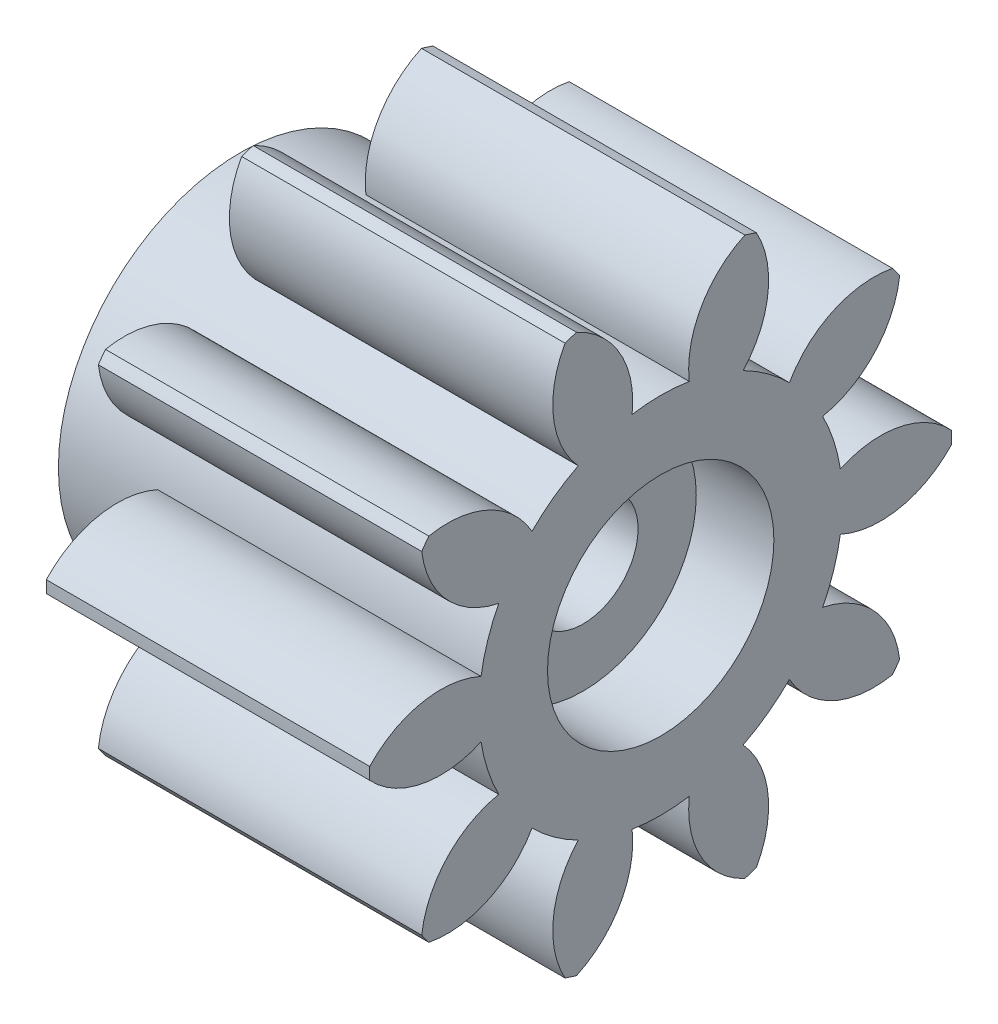
SolidWorks part; units mm, degrees
material "7075-O (SS)"
ref_plane "Plane1" through (0, 0, 0) normal (0, 0, 1) x (1, 0, 0)
ref_plane "Plane2" through (0, 0, 0) normal (0, 1, 0) x (1, 0, 0)
ref_plane "Plane3" through (0, 0, 0) normal (1, 0, 0) x (0, 0, -1)
sketch "HoldingSke" plane through (0, 0, 0) normal (0, 1, 0) x (1, 0, 0)
  line L0 (0, 0) -> (0.6565, -0.1158)
  line L1 (-15, 0) -> (100, 0) construction
  line L2 (0, 0) -> (-2.1039, 2.3779)
  line L3 (0, 0) -> (-11.863, 4.5341)
  line L4 (0, 0) -> (8.5048, 1.4996)
  line L5 (0, 0) -> (-46.8476, -17.4728)
  line L6 (0, 0) -> (-8.2896, -5.593)
  line L7 (-2.1039, 2.3779) -> (8.6589, 51.2074)
  line L8 (-76.2, 54.61) -> (-76.1, 54.61)
  line L9 (-71.009, 38.7566) -> (-53.1078, 45.2721)
  line L10 (-76.2, 71.12) -> (104.1128, 71.12)
  line L11 (0, 0) -> (-10, 0)
  line L12 (-76.2, 101.6) -> (-76.147, 101.6)
  line L13 (24.9733, 27.94) -> (52.9518, 28.4284)
  line L14 (24.9733, 27.94) -> (24.9743, 27.94)
  line L15 (24.9733, 27.94) -> (100.4006, 29.5858)
  line L16 (-63.627, -1.5) -> (-12.827, -1.5)
  circle A0 centre (0, 0) radius 0.4
  circle A1 centre (0, 0) radius 5.624
  circle A2 centre (0, 0) radius 37.5
  circle A3 centre (0, 0) radius 0.4
  dimension "MHD" = 11.248
  dimension "Hub_dia" = 75
  dimension "Bore" = 0.8
  dimension "MBD" = 0.8
  dimension "Num_teeth" = 10
  dimension "Pitch" = 0.6667
  dimension "Overall_len" = 50
  dimension "Show_teeth" = 10
  dimension "Thickness" = 10
  dimension "OAL" = 50.0016
  dimension "T_dim" = 0.1
  dimension "Ap" = 20
  dimension "H" = 19.05
  dimension "Pitch_radius" = 180.3128
  dimension "Width" = 10
  dimension "Backlash" = 0.053
  dimension "Addendum_fac" = 1
  dimension "Dedendum_fac" = 1.25
  dimension "Clearance_fac" = 0.25
  dimension "Dedendum_add" = 0.001
  dimension "Module" = 1.5
sketch "BasProSke" plane through (0, 0, 0) normal (0, 1, 0) x (1, 0, 0)
  line L0 (-10, 0) -> (60, 0) construction
  line L1 (0, 0) -> (0, 9)
  line L2 (0, 0) -> (10, 0)
  line L3 (10, 0) -> (10, 9)
  line L4 (10, 9) -> (0, 9)
  dimension "Thickness" = 10
  dimension "Diameter" = 18
revolve "Base-Revolve" add sketch "BasProSke" angle 360 about L0
sketch "TooCutSke" plane through (0, 0, 0) normal (1, 0, 0) x (0, 0, -1)
  line L1 (0, 0) -> (0, 107) construction
  line L2 (0, 0) -> (-1.2658, 7.3924) construction
  line L3 (0, 0) -> (-4.5869, 14.117) construction
  line L4 (-1.2658, 7.3924) -> (-2.2934, 7.0585) construction
  arc A0 (0.8839, 5.5541) -> (-0.8839, 5.5541) centre (0, 0) ccw
  arc A1 (2.6378, 8.6313) -> (-2.6378, 8.6313) centre (0, 0) ccw
  circle A2 centre (0, 0) radius 7.5 construction
  circle A3 centre (0, 0) radius 7.0477 construction
  arc A4 (-0.8839, 5.5541) -> (-2.6378, 8.6313) centre (-3.8646, 5.8936) ccw
  arc A5 (2.6378, 8.6313) -> (0.8839, 5.5541) centre (3.8646, 5.8936) ccw
  dimension "Root_dia" = 11.248
  dimension "Overcut_dia" = 18.0508
  dimension "Pitch_dia" = 15
  dimension "Base_dia" = 14.0954
  dimension "Flank_rad" = 3
  dimension "Half_ang" = 18
  dimension "Half_CT" = 1.0805
extrude "ToothCut" cut sketch "TooCutSke" along normal through all
fillet "Breaks" [suppressed] radius 0.03 tangent propagation no
fillet "RootFillets" [suppressed] radius 0.376
pattern_circular "TeethCuts" count 10 over 360 about axis through (-10, 0, 0) along (1, 0, 0) of "ToothCut", "RootFillets", "Breaks"
sketch "HubNeaOneSke" plane through (0, 0, 0) normal (-1, 0, 0) x (0, 0, 1)
  circle A0 centre (0, 0) radius 5.624
  dimension "Diameter" = 11.248
extrude "HubNearOne" [suppressed] add sketch "HubNeaOneSke" along normal blind 40.0016
sketch "HubNeaBotSke" plane through (0, 0, 0) normal (-1, 0, 0) x (0, 0, 1)
  circle A0 centre (0, 0) radius 5.624
  dimension "Diameter" = 11.248
extrude "HubNearBoth" [suppressed] add sketch "HubNeaBotSke" along normal blind 20.0008
ref_plane "FarPln" through (10, 0, 0) normal (1, 0, 0) x (0, 0, -1)
sketch "HubFarSke" plane through (10, 0, 0) normal (1, 0, 0) x (0, 0, -1)
  circle A0 centre (0, 0) radius 5.624
  dimension "Diameter" = 11.248
extrude "HubFar" [suppressed] add sketch "HubFarSke" along normal blind 20.0008
sketch "KeySke" plane through (0, 0, 0) normal (1, 0, 0) x (0, 0, -1)
  line L0 (-0.05, 0) -> (-0.05, 0.5)
  line L1 (-0.05, 0.5) -> (0.05, 0.5)
  line L2 (0.05, 0.5) -> (0.05, 0)
  line L3 (0, 0) -> (0, 34) construction
  line L4 (-0.05, 0) -> (0.05, 0)
  dimension "Offset" = 0.5
  dimension "Width" = 0.1
extrude "Keyway" [suppressed] cut sketch "KeySke" along normal mid plane 100.0031
pattern_circular "Keyway2" [suppressed] count 2 every 90 about axis through (-10, 0, 0) along (1, 0, 0) reverse direction yes
sketch "Croquis2" plane through (0, 0, 0) normal (-1, 0, 0) x (0, 0, 1)
  circle A0 centre (0, 0) radius 5.624
  arc A1 (5.5554, 0.8757) -> (5.0091, 2.5569) centre (0, 0) ccw construction
extrude "Saliente-Extruir2" add sketch "Croquis2" along normal blind 3
hole_wizard "Refrentado para tornillo con cabeza troncocónica de M31" positions "Croquis3" profile "Croquis4" counterbore size "M3" standard "Ansi Metric" end condition up to next
sketch "Croquis3" plane through (10, 0, 0) normal (1, 0, 0) x (0, 0, -1)
  point P0 (0, 0)
sketch "Croquis4" plane through (10, 0, 0) normal (0, 1, 0) x (0, 0, -1)
  line L0 (0, 0) -> (0, 13)
  line L1 (0, 13) -> (1.7, 13)
  line L3 (1.7, 13) -> (1.7, 2.4)
  line L4 (1.7, 2.4) -> (3.5, 2.4)
  line L5 (3.5, 2.4) -> (3.5, 0)
  line L7 (3.5, 0) -> (0, 0)
  line L11 (0, -6.35) -> (0, 107.95) construction
  dimension "Diámetro de taladro hasta el siguiente" = 3.4
  dimension "Profundidad de taladro hasta el siguiente" = 13
  dimension "Diámetro de refrentado" = 7
  dimension "Profundidad de refrentado" = 2.4
sketch "Croquis5" plane through (-3, 0, 0) normal (-1, 0, 0) x (0, 0, 1)
  line L0 (0, 0) -> (0, 3.6) construction
  circle A0 centre (0, 3.6) radius 1
  circle A3 centre (3.1177, -1.8) radius 1
  circle A4 centre (-3.1177, -1.8) radius 1
  circle A6 centre (0, 0) radius 1.7 construction
  dimension "D1" = 2
  dimension "D3" = 3.6
  dimension "D2" = 3
extrude "Cortar-Extruir1" cut sketch "Croquis5" against normal blind 3
equation "' \"Module@HoldingSke\" = 6.35"
equation "' \"Num_teeth@HoldingSke\" = 12"
equation "' \"Ap@HoldingSke\" =  20"
equation "' \"Ap@HoldingSke\" = 20"
equation "' \"Width@HoldingSke\" = 0.5 * 25.4"
equation "' \"Hub_dia@HoldingSke\"= 1 * 25.4"
equation "' \"Hub_dia@HoldingSke\" = 1 * 25.4"
equation "' \"Overall_len@HoldingSke\" = 1.0 * 25.4"
equation "' \"Bore@HoldingSke\" = 0.75 * 25.4"
equation "' \"T_dim@HoldingSke\" = 0.1 * 25.4"
equation "' \"Width@KeySke\" = 0.25 * 25.4"
equation "' \"Show_teeth@HoldingSke\" = 13"
equation "' \"Backlash@HoldingSke\" = 0.009 * 25.4"
equation "' \"Addendum_fac@HoldingSke\" = 1.0"
equation "' \"Dedendum_fac@HoldingSke\" = 1.25"
equation "' \"Dedendum_add@HoldingSke\" = 0.00005 * 25.4"
equation "' \"Clearance_fac@HoldingSke\" = 0.25"
equation "\"Pitch@HoldingSke\" = 1 / \"Module@HoldingSke\""
equation "\"Overcut_dia@TooCutSke\" = (\"Num_teeth@HoldingSke\" + 2 * \"Addendum_fac@HoldingSke\") / \"Pitch@HoldingSke\" + 0.002 * 25.4"
equation "\"Pitch_dia@TooCutSke\" = \"Num_teeth@HoldingSke\" / \"Pitch@HoldingSke\""
equation "\"Base_dia@TooCutSke\" = \"Num_teeth@HoldingSke\" / \"Pitch@HoldingSke\" * cos((\"Ap@HoldingSke\"  * 3.14159265 / 180))"
equation "\"Root_dia@TooCutSke\" = (\"Num_teeth@HoldingSke\" + 2) / \"Pitch@HoldingSke\" - 2 * (\"Addendum_fac@HoldingSke\" + \"Dedendum_fac@HoldingSke\") / \"Pitch@HoldingSke\" - \"Dedendum_add@HoldingSke\" * 2"
equation "\"Half_ang@TooCutSke\" = 180 / \"Num_teeth@HoldingSke\""
equation "\"Half_CT@TooCutSke\" = \"Num_teeth@HoldingSke\" / \"Pitch@HoldingSke\" * sin((3.14159265 / 2 / \"Num_teeth@HoldingSke\")) / 2 - 7 * \"Backlash@HoldingSke\" / 4"
equation "\"Flank_rad@TooCutSke\" = \"Num_teeth@HoldingSke\" / \"Pitch@HoldingSke\" / 5"
equation "\"Radius@RootFillets\" = \"Clearance_fac@HoldingSke\" / \"Pitch@HoldingSke\" + \"Dedendum_add@HoldingSke\""
equation "\"Break_rad@Breaks\" = 0.02 / \"Pitch@HoldingSke\""
equation "\"Thickness@HoldingSke\" = \"Width@HoldingSke\""
equation "\"OAL@HoldingSke\" = \"Thickness@HoldingSke\""
equation "\"MHD@HoldingSke\" = (\"Num_teeth@HoldingSke\" + 2) / \"Pitch@HoldingSke\" - 2 * (\"Addendum_fac@HoldingSke\" + \"Dedendum_fac@HoldingSke\")  / \"Pitch@HoldingSke\" - \"Dedendum_add@HoldingSke\" * 2"
equation "\"MBD@HoldingSke\" = (\"Num_teeth@HoldingSke\" + 2) / \"Pitch@HoldingSke\" - 2 * (\"Addendum_fac@HoldingSke\" + \"Dedendum_fac@HoldingSke\")  / \"Pitch@HoldingSke\" - \"Dedendum_add@HoldingSke\" * 2 - 0.002 * 25.4"
equation "\"MHD@HoldingSke\" = ((sgn( \"MHD@HoldingSke\" - \"Hub_dia@HoldingSke\" )-1)*( \"MHD@HoldingSke\" - \"Hub_dia@HoldingSke\" ))/-2+ \"Hub_dia@HoldingSke\""
equation "\"MBD@HoldingSke\" = ((sgn( \"MBD@HoldingSke\" - \"Bore@HoldingSke\" )-1)*( \"MBD@HoldingSke\" - \"Bore@HoldingSke\" ))/-2+ \"Bore@HoldingSke\""
equation "\"OAL@HoldingSke\" = ((sgn( \"OAL@HoldingSke\" - \"Overall_len@HoldingSke\" )+1)*( \"OAL@HoldingSke\" - \"Overall_len@HoldingSke\" ))/2 + \"Overall_len@HoldingSke\" + 0.000002 * 25.4"
equation "\"Num_teeth@TeethCuts\" = int( \"Show_teeth@HoldingSke\" ) + 1"
equation "\"Num_teeth@TeethCuts\" = ((sgn( \"Num_teeth@TeethCuts\" - \"Num_teeth@HoldingSke\" )-1)*( \"Num_teeth@TeethCuts\" - \"Num_teeth@HoldingSke\" ))/-2+ \"Num_teeth@HoldingSke\""
equation "\"Num_teeth@TeethCuts\" = ((sgn( \"Num_teeth@TeethCuts\" - 2.0)+1)*( \"Num_teeth@TeethCuts\" - 2.0))/2 +2.0"
equation "\"Angle@TeethCuts\" = 360.0 / \"Num_teeth@HoldingSke\""
equation "\"Diameter@BasProSke\" = (\"Num_teeth@HoldingSke\" + 2 * \"Addendum_fac@HoldingSke\") / \"Pitch@HoldingSke\""
equation "\"Thickness@BasProSke\"  = \"Thickness@HoldingSke\""
equation "' \"Fillet_rad@BasProSke\" =  \"Thickness@HoldingSke\" * 0.05"
equation "' \"Fillet_rad@BasProSke\" = \"Thickness@HoldingSke\" * 0.05"
equation "\"MHD@HoldingSke\" = ((sgn( \"MHD@HoldingSke\" - \"Root_dia@TooCutSke\" )-1)*( \"MHD@HoldingSke\" - \"Root_dia@TooCutSke\" ))/-2+ \"Root_dia@TooCutSke\""
equation "\"Diameter@HubNeaOneSke\" = \"MHD@HoldingSke\""
equation "\"Length@HubNearOne\" = \"OAL@HoldingSke\" - \"Thickness@BasProSke\""
equation "\"Diameter@HubNeaBotSke\" = \"MHD@HoldingSke\""
equation "\"Length@HubNearBoth\" = ( \"OAL@HoldingSke\" - \"Thickness@BasProSke\" ) / 2.0"
equation "\"Thickness@FarPln\" = \"Thickness@BasProSke\""
equation "\"Diameter@HubFarSke\" = \"MHD@HoldingSke\""
equation "\"Length@HubFar\" = ( \"OAL@HoldingSke\" - \"Thickness@BasProSke\" ) / 2.0"
equation "\"Diameter@BorSke\" = \"MBD@HoldingSke\""
equation "\"D1@Bore\" = \"OAL@HoldingSke\" * 2.0"
equation "\"D1@Keyway\" = \"OAL@HoldingSke\" * 2.0"
equation "\"Offset@KeySke\" = \"T_dim@HoldingSke\" + \"MBD@HoldingSke\" / 2.0"
